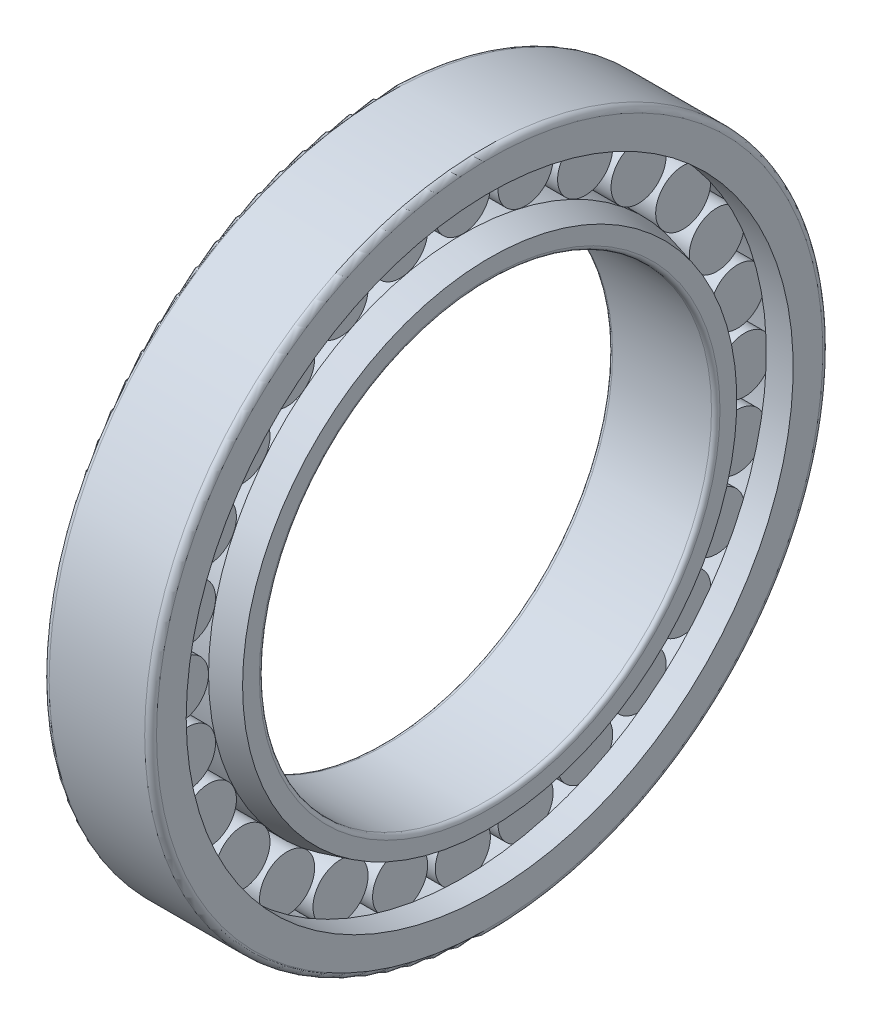
SolidWorks part; units mm, degrees
ref_plane "基准面1" through (0, 0, 0) normal (0, 0, 1) x (1, 0, 0)
ref_plane "基准面2" through (0, 0, 0) normal (0, 1, 0) x (1, 0, 0)
ref_plane "基准面3" through (0, 0, 0) normal (1, 0, 0) x (0, 0, -1)
sketch "尺寸草图" plane through (0, 0, 0) normal (0, 0, 1) x (1, 0, 0)
  line L0 (0, 0) -> (1.5, 0)
  line L1 (1.5, 0) -> (3.6, 0)
  line L2 (3.6, 0) -> (41.6, 0)
  line L3 (41.6, 0) -> (201.6, 0)
  line L4 (201.6, 0) -> (381.6, 0)
  line L5 (381.6, 0) -> (621.6, 0)
  dimension "倒角小" = 1.5
  dimension "倒角大" = 2.1
  dimension "w" = 38
  dimension "d2" = 160
  dimension "参考FW" = 180
  dimension "d1" = 240
sketch "草图2" plane through (0, 0, 0) normal (0, 0, 1) x (1, 0, 0)
  line L0 (-10.0801, 0) -> (21.9267, 0) construction
  line L1 (9.5, 90) -> (28.5, 90)
  line L2 (0, 86.5423) -> (9.5, 90)
  line L3 (0, 86.5423) -> (0, 81.5)
  line L4 (1.5, 80) -> (36.5, 80)
  line L5 (38, 87.4545) -> (38, 81.5)
  line L7 (38, 87.4545) -> (28.5, 90)
  arc A0 (36.5, 80) -> (38, 81.5) centre (36.5, 81.5) ccw
  arc A1 (0, 81.5) -> (1.5, 80) centre (1.5, 81.5) ccw
  point P13 (38, 80)
  point P16 (0, 80)
  dimension "D1" = 1.5
  dimension "DD" = 160
  dimension "D2" = 38
  dimension "D3" = 15
  dimension "FW" = 180
  dimension "D4" = 20
revolve "基体-旋转" add sketch "草图2" angle 360 about L0
sketch "草图4" plane through (0, 0, 0) normal (0, 0, 1) x (1, 0, 0)
  line L0 (0, 0) -> (17.8006, 0) construction
  line L1 (-10.0801, 0) -> (21.9267, 0) construction
  line L2 (28.5, 107.4) -> (38, 107.4)
  line L3 (2.1, 120) -> (35.9, 120)
  line L4 (0, 117.9) -> (0, 107.4)
  line L5 (0, 107.4) -> (9.5, 107.4)
  line L6 (38, 117.9) -> (38, 107.4)
  line L7 (9.5, 109.5) -> (28.5, 109.5)
  line L8 (9.5, 109.5) -> (9.5, 107.4)
  line L10 (28.5, 109.5) -> (28.5, 107.4)
  arc A0 (35.9, 120) -> (38, 117.9) centre (35.9, 117.9) cw
  arc A1 (2.1, 120) -> (0, 117.9) centre (2.1, 117.9) ccw
  point P15 (38, 120)
  point P18 (0, 120)
  dimension "D2" = 2.1
  dimension "D1" = 219
  dimension "B" = 38
  dimension "D" = 240
  dimension "D3" = 2.1
revolve "凸台-旋转2" add sketch "草图4" angle 360 about L0
sketch "草图3" plane through (0, 0, 0) normal (0, 0, 1) x (1, 0, 0)
  line L0 (28.5, 99.75) -> (9.5, 99.75) construction
  line L1 (9.5, 99.75) -> (28.5, 99.75)
  line L3 (0, 0) -> (38, 0) construction
  line L4 (38, -81.5) -> (38, 81.5) construction
  line L5 (28.5, 90) -> (28.5, -90) construction
  line L6 (9.5, 109.5) -> (28.5, 109.5)
  line L7 (9.5, 109.5) -> (9.5, 99.75)
  line L8 (9.5, 90) -> (28.5, 90) construction
  line L9 (28.5, 109.5) -> (28.5, 99.75)
  line L10 (28.5, 107.4) -> (28.5, -107.4) construction
  line L11 (9.5, 109.5) -> (9.5, 107.4) construction
  line L12 (9.5, 109.5) -> (28.5, 109.5) construction
  line L13 (9.5, 90) -> (28.5, 90) construction
  line L15 (28.5, 109.5) -> (28.5, 90) construction
revolve "凸台-旋转1" add sketch "草图3" angle 360 about L1
ref_axis "基准轴1" through (-80.9, 0, 0) along (1, 0, 0)
pattern_circular "阵列(圆周)2" count 28 over 360 about axis through (-80.9, 0, 0) along (1, 0, 0) reverse direction yes of bodies 102
